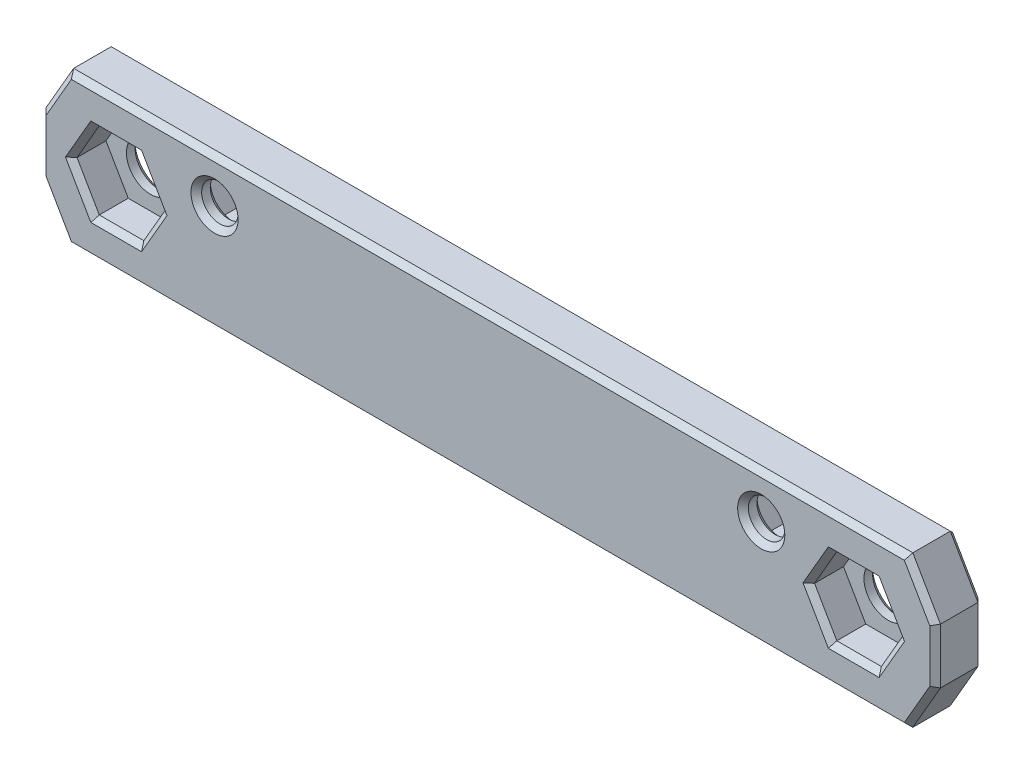
SolidWorks part; units mm, degrees
ref_plane "Front Plane" through (0, 0, 0) normal (0, 0, 1) x (1, 0, 0)
ref_plane "Top Plane" through (0, 0, 0) normal (0, 1, 0) x (1, 0, 0)
ref_plane "Right Plane" through (0, 0, 0) normal (1, 0, 0) x (0, 0, -1)
sketch "Sketch1" plane through (0, 0, 0) normal (0, 0, 1) x (1, 0, 0)
  line L1 (46, -37.5) -> (-46, -37.5)
  line L2 (46, -37.5) -> (46, 37.5)
  line L3 (46, 37.5) -> (-46, 37.5)
  line L4 (-46, -37.5) -> (-46, 37.5)
  line L5 (46, -37.5) -> (-46, 37.5) construction
  line L6 (46, 37.5) -> (-46, -37.5) construction
  point P0 (0, 0)
  dimension "D1" = 92
  dimension "D2" = 75
extrude "Boss-Extrude1" add sketch "Sketch1" along normal blind 4.5
sketch "Sketch2" plane through (0, 0, 4.5) normal (0, 0, 1) x (1, 0, 0)
  line L0 (-34.6699, -1.6) -> (34.1301, -1.6) construction
  line L1 (46, 37.5) -> (-46, 37.5) construction
  dimension "D1" = 39.1
  dimension "D2" = 34.1301
  dimension "D3" = 68.8
hole_wizard "M4 Clearance Hole1" positions "Sketch3" profile "Sketch4" hole size "M4" standard "DIN" end condition through all
sketch "Sketch3" plane through (0, 0, 4.5) normal (0, 0, 1) x (1, 0, 0)
  point P0 (-34.6699, -1.6)
  point P3 (34.1301, -1.6)
sketch "Sketch4" plane through (-34.6699, -1.6, 4.5) normal (1, 0, 0) x (0, -1, 0)
  line L0 (0, 0) -> (0, 4.5)
  line L1 (0, 4.5) -> (2.25, 4.5)
  line L2 (2.25, 4.5) -> (2.25, 0)
  line L5 (2.25, 0) -> (0, 0)
  line L11 (0, -6.35) -> (0, 107.95) construction
  dimension "Thru Hole Dia." = 4.5
  dimension "Thru Hole Depth" = 4.5
sketch "Sketch5" plane through (0, 0, 4.5) normal (0, 0, 1) x (1, 0, 0)
  line L0 (-25.5, 1.4) -> (25.5, 1.4)
  line L2 (-34.6699, -1.6) -> (34.1301, -1.6) construction
  dimension "D1" = 51
  dimension "D2" = 25.5
  dimension "D3" = 3
hole_wizard "M3 Clearance Hole1" positions "Sketch6" profile "Sketch7" hole size "M3" standard "DIN" end condition through all
sketch "Sketch6" plane through (0, 0, 4.5) normal (0, 0, 1) x (1, 0, 0)
  point P0 (-25.5, 1.4)
  point P3 (25.5, 1.4)
sketch "Sketch7" plane through (-25.5, 1.4, 4.5) normal (1, 0, 0) x (0, -1, 0)
  line L0 (0, 0) -> (0, 4.5)
  line L1 (0, 4.5) -> (1.7, 4.5)
  line L2 (1.7, 4.5) -> (1.7, 0)
  line L5 (1.7, 0) -> (0, 0)
  line L11 (0, -6.35) -> (0, 107.95) construction
  dimension "Thru Hole Dia." = 3.4
  dimension "Thru Hole Depth" = 4.5
sketch "Sketch8" plane through (0, 0, 4.5) normal (0, 0, 1) x (1, 0, 0)
  line L1 (-30.513, -1.6) -> (-32.5914, 2)
  line L2 (-32.5914, 2) -> (-36.7483, 2)
  line L3 (-36.7483, 2) -> (-38.8268, -1.6)
  line L4 (-38.8268, -1.6) -> (-36.7483, -5.2)
  line L5 (-36.7483, -5.2) -> (-32.5914, -5.2)
  line L6 (-32.5914, -5.2) -> (-30.513, -1.6)
  line L7 (29.9732, -1.6) -> (32.0517, -5.2)
  line L8 (32.0517, -5.2) -> (36.2086, -5.2)
  line L9 (36.2086, -5.2) -> (38.287, -1.6)
  line L10 (38.287, -1.6) -> (36.2086, 2)
  line L11 (36.2086, 2) -> (32.0517, 2)
  line L12 (32.0517, 2) -> (29.9732, -1.6)
  circle A0 centre (-34.6699, -1.6) radius 3.6 construction
  circle A1 centre (34.1301, -1.6) radius 3.6 construction
  dimension "D1" = 7.2
extrude "Cut-Extrude1" cut sketch "Sketch8" against normal blind 3.2
sketch "Sketch9" plane through (0, 0, 0) normal (0, 0, -1) x (-1, 0, 0)
  line L1 (-22.2091, 1.4) -> (-23.8546, 4.25)
  line L2 (-23.8546, 4.25) -> (-27.1454, 4.25)
  line L3 (-27.1454, 4.25) -> (-28.7909, 1.4)
  line L4 (-28.7909, 1.4) -> (-27.1454, -1.45)
  line L5 (-27.1454, -1.45) -> (-23.8546, -1.45)
  line L6 (-23.8546, -1.45) -> (-22.2091, 1.4)
  line L7 (22.2091, 1.4) -> (23.8546, -1.45)
  line L8 (23.8546, -1.45) -> (27.1454, -1.45)
  line L9 (27.1454, -1.45) -> (28.7909, 1.4)
  line L10 (28.7909, 1.4) -> (27.1454, 4.25)
  line L11 (27.1454, 4.25) -> (23.8546, 4.25)
  line L12 (23.8546, 4.25) -> (22.2091, 1.4)
  circle A0 centre (-25.5, 1.4) radius 2.85 construction
  circle A1 centre (25.5, 1.4) radius 2.85 construction
  dimension "D1" = 5.7
extrude "Cut-Extrude2" cut sketch "Sketch9" against normal blind 2.7
sketch "Sketch10" plane through (0, 0, 0) normal (0, 0, -1) x (-1, 0, 0)
  line L0 (46, 37.5) -> (46, -37.5) construction
  line L1 (-46, 37.5) -> (46, 37.5)
  line L2 (-46, 37.5) -> (-46, 8.25)
  line L3 (-46, 8.25) -> (46, 8.25)
  line L4 (46, 37.5) -> (46, 8.25)
  line L5 (-23.8546, 4.25) -> (-27.1454, 4.25) construction
  line L6 (-46, -37.5) -> (46, -37.5)
  line L7 (-46, -37.5) -> (-46, -9.2)
  line L8 (-46, -9.2) -> (46, -9.2)
  line L9 (46, -37.5) -> (46, -9.2)
  line L10 (-32.0517, -5.2) -> (-36.2086, -5.2) construction
  dimension "D1" = 4
  dimension "D2" = 4
extrude "Cut-Extrude3" cut sketch "Sketch10" against normal through all
sketch "Sketch11" plane through (0, 0, 4.5) normal (0, 0, 1) x (1, 0, 0)
  line L0 (-39.1394, 5.45) -> (-41.7199, 0.9805)
  line L3 (-41.7199, 0.9805) -> (-41.7199, -4.1805)
  line L4 (-41.7199, -4.1805) -> (-39.1394, -8.65)
  line L6 (-39.1394, -8.65) -> (0, -8.65)
  line L7 (0, -8.65) -> (0, -18.65)
  line L8 (0, -18.65) -> (-51, -18.65)
  line L9 (-51, -18.65) -> (-51, 15.45)
  line L10 (-51, 15.45) -> (0, 15.45)
  line L12 (-39.1394, 5.45) -> (0, 5.45)
  line L13 (0, 5.45) -> (0, 15.45)
  line L14 (-36.7483, 2) -> (-38.8268, -1.6) construction
  line L15 (-38.8268, -1.6) -> (-36.7483, -5.2) construction
  line L16 (-27.1454, 4.25) -> (-23.8546, 4.25) construction
  line L18 (-36.7483, -5.2) -> (-32.5914, -5.2) construction
  line L20 (-46, 8.25) -> (-46, -9.2) construction
  point P10 (-41.7199, -1.6)
  dimension "D1" = 1.2
  dimension "D2" = 3.45
  dimension "D3" = 7.05
  dimension "D4" = 7.05
  dimension "D5" = 46
  dimension "D6" = 10
  dimension "D7" = 10
  dimension "D8" = 5
extrude "Cut-Extrude4" cut sketch "Sketch11" against normal blind 10
mirror "Mirror1" about plane through (0, 0, 0) normal (1, 0, 0) of "Cut-Extrude4"
chamfer "Chamfer1" distance 0.5 angle 45 44 edges at (41.7199, -1.6, 4.5) (40.4296, -6.4152, 4.5) (0, -8.65, 4.5) (-40.4296, -6.4152, 4.5) (-41.7199, -1.6, 4.5) (-40.4296, 3.2152, 4.5) (0, 5.45, 4.5) (40.4296, 3.2152, 4.5) (27.2, 1.4, 4.5) (-23.8, 1.4, 4.5) (31.0124, -3.4, 4.5) (34.1301, -5.2, 4.5) (37.2478, -3.4, 4.5) (37.2478, 0.2, 4.5) (34.1301, 2, 4.5) (31.0124, 0.2, 4.5) (-31.5522, 0.2, 4.5) (-34.6699, 2, 4.5) (-37.7876, 0.2, 4.5) (-37.7876, -3.4, 4.5) (-34.6699, -5.2, 4.5) (-31.5522, -3.4, 4.5) (-40.4296, 3.2152, 0) (-41.7199, -1.6, 0) (-40.4296, -6.4152, 0) (0, -8.65, 0) (40.4296, -6.4152, 0) (41.7199, -1.6, 0) (40.4296, 3.2152, 0) (0, 5.45, 0) (25.5, 4.25, 0) (27.9682, 2.825, 0) (27.9682, -0.025, 0) (25.5, -1.45, 0) (23.0318, -0.025, 0) (23.0318, 2.825, 0) (-25.5, -1.45, 0) (-27.9682, -0.025, 0) (-27.9682, 2.825, 0) (-25.5, 4.25, 0) (-23.0318, 2.825, 0) (-23.0318, -0.025, 0) (-32.4199, -1.6, 0) (36.3801, -1.6, 0)
chamfer "Chamfer2" distance 0.5 angle 45 2 edges at (-27.2, 1.4, 2.7) (23.8, 1.4, 2.7)
